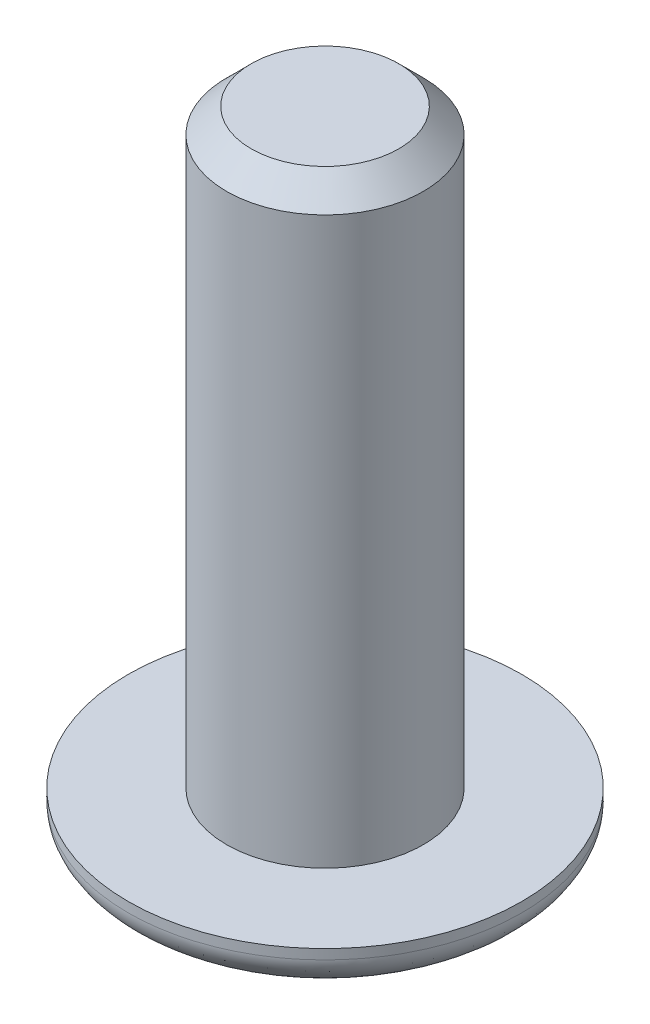
SolidWorks part; units mm, degrees
material "ASTM A36 钢"
ref_plane "前视基准面" through (0, 0, 0) normal (0, 0, 1) x (1, 0, 0)
ref_plane "上视基准面" through (0, 0, 0) normal (0, 1, 0) x (1, 0, 0)
ref_plane "右视基准面" through (0, 0, 0) normal (1, 0, 0) x (0, 0, -1)
sketch "草图1" plane through (0, 0, 0) normal (0, 1, 0) x (1, 0, 0)
  line L1 (1.4434, 0) -> (0.7217, 1.25)
  line L2 (0.7217, 1.25) -> (-0.7217, 1.25)
  line L3 (-0.7217, 1.25) -> (-1.4434, 0)
  line L4 (-1.4434, 0) -> (-0.7217, -1.25)
  line L5 (-0.7217, -1.25) -> (0.7217, -1.25)
  line L6 (0.7217, -1.25) -> (1.4434, 0)
  circle A0 centre (0, 0) radius 4
  circle A1 centre (0, 0) radius 1.25 construction
extrude "凸台-拉伸1" add sketch "草图1" along normal blind 1.2
sketch "草图2" plane through (0, 1.2, 0) normal (0, 1, 0) x (1, 0, 0)
  circle A0 centre (0, 0) radius 2
extrude "凸台-拉伸2" add sketch "草图2" along normal blind 12
chamfer "倒角1" distance 0.5 angle 45 1 edges at (0, 13.2, 2)
fillet "圆角1" radius 2 1 edges at (0, 0, 4) second distance 1 first distance on face at (0, 0, 4)
